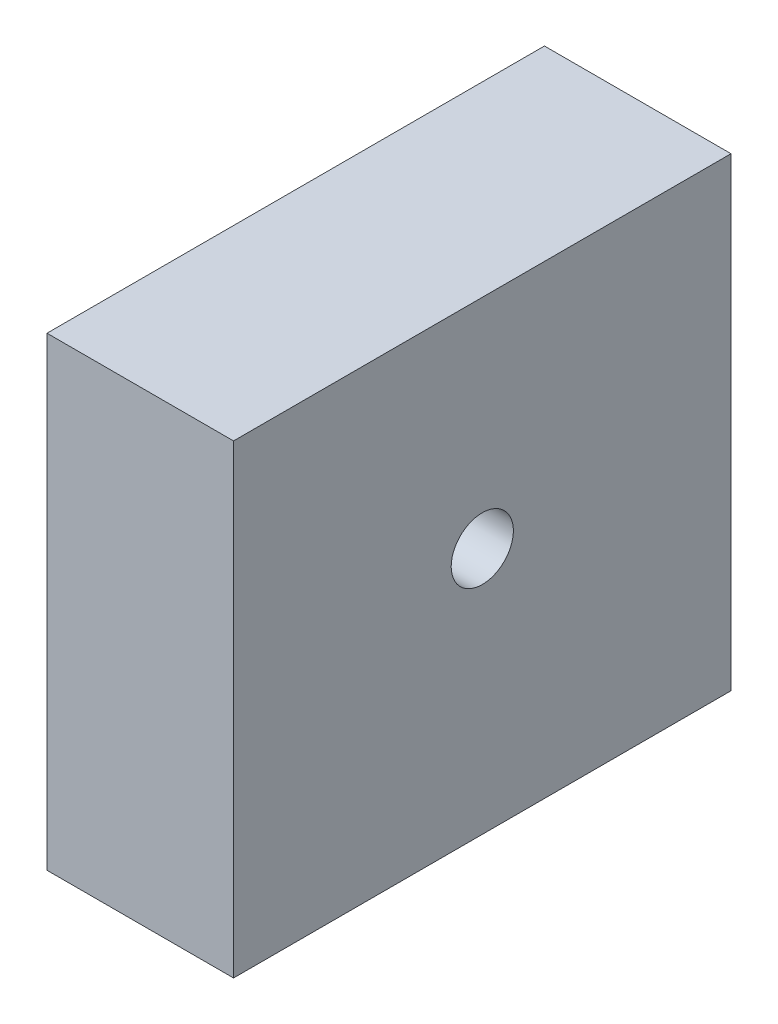
SolidWorks part; units mm, degrees
ref_plane "Front Plane" through (0, 0, 0) normal (0, 0, 1) x (1, 0, 0)
ref_plane "Top Plane" through (0, 0, 0) normal (0, 1, 0) x (1, 0, 0)
ref_plane "Right Plane" through (0, 0, 0) normal (1, 0, 0) x (0, 0, -1)
sketch "Sketch1" plane through (0, 0, 0) normal (0, 1, 0) x (1, 0, 0)
  line L1 (-9.525, 25.4) -> (9.525, 25.4)
  line L2 (-9.525, 25.4) -> (-9.525, -25.4)
  line L3 (-9.525, -25.4) -> (9.525, -25.4)
  line L4 (9.525, 25.4) -> (9.525, -25.4)
  line L5 (-9.525, 25.4) -> (9.525, -25.4) construction
  line L6 (-9.525, -25.4) -> (9.525, 25.4) construction
  point P0 (0, 0)
  dimension "D1" = 19.05
  dimension "D2" = 50.8
extrude "Boss-Extrude1" add sketch "Sketch1" along normal blind 47.498
hole_wizard "1/4 (0.2500) Dowel Hole1" positions "Sketch2" profile "Sketch3" hole size "1/4" standard "ANSI Inch" end condition through all
sketch "Sketch2" plane through (-9.525, 0, 0) normal (-1, 0, 0) x (0, 0, 1)
  point P0 (0, 25.273)
sketch "Sketch3" plane through (-9.525, 25.273, 0) normal (0, 1, 0) x (0, 0, 1)
  line L0 (0, 0) -> (0, 19.05)
  line L1 (0, 19.05) -> (3.175, 19.05)
  line L2 (3.175, 19.05) -> (3.175, 0)
  line L5 (3.175, 0) -> (0, 0)
  line L11 (0, -6.35) -> (0, 107.95) construction
  dimension "Thru Hole Dia." = 6.35
  dimension "Thru Hole Depth" = 19.05
